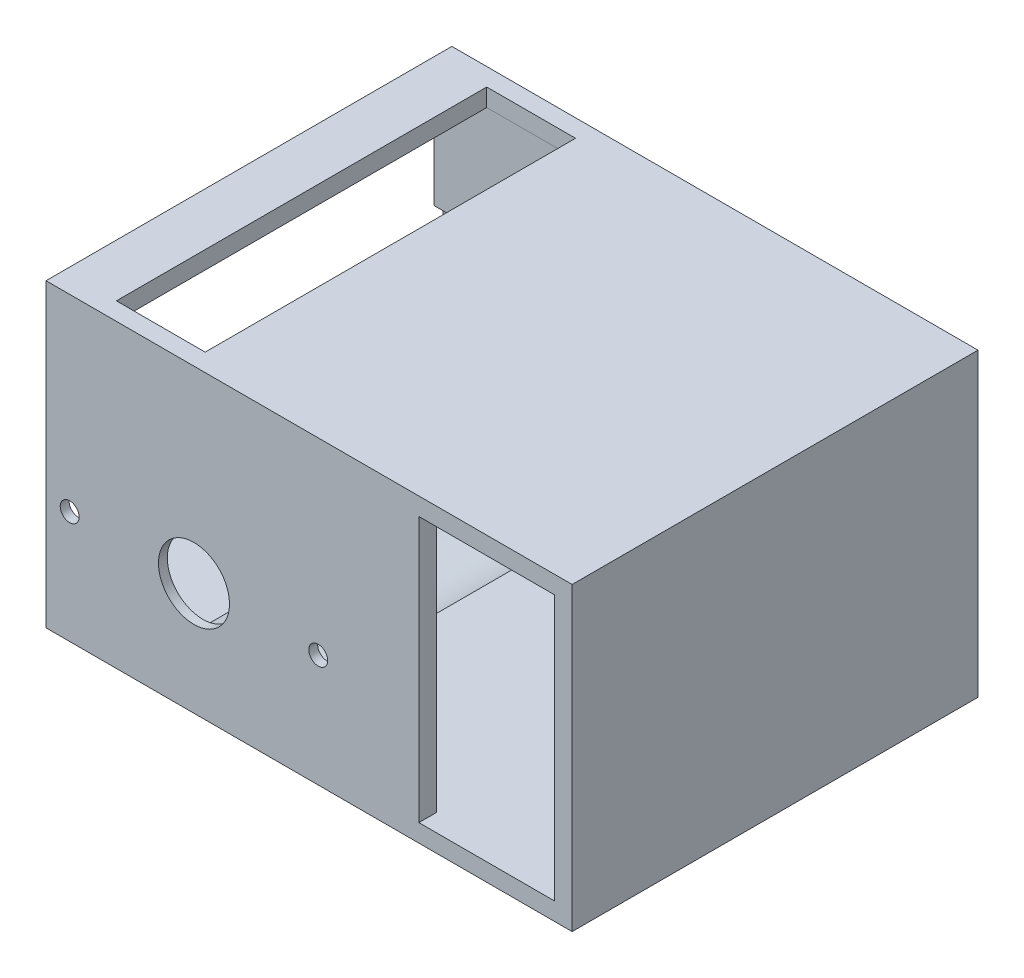
SolidWorks part; units mm, degrees
ref_plane "Front Plane" through (0, 0, 0) normal (0, 0, 1) x (1, 0, 0)
ref_plane "Top Plane" through (0, 0, 0) normal (0, 1, 0) x (1, 0, 0)
ref_plane "Right Plane" through (0, 0, 0) normal (1, 0, 0) x (0, 0, -1)
sketch "Sketch1" plane through (0, 0, 0) normal (0, 0, 1) x (1, 0, 0)
  line L1 (0, 0) -> (88.9, 0)
  line L2 (0, 0) -> (0, 50.8)
  line L3 (0, 50.8) -> (88.9, 50.8)
  line L4 (88.9, 0) -> (88.9, 50.8)
extrude "Boss-Extrude1" add sketch "Sketch1" along normal blind 68.58
sketch "Sketch2" plane through (0, 0, 68.58) normal (0, 0, 1) x (1, 0, 0)
  line L3 (63, 47.8) -> (85.9, 47.8)
  line L4 (63, 47.8) -> (63, 3)
  line L5 (63, 3) -> (85.9, 3)
  line L6 (85.9, 47.8) -> (85.9, 3)
  circle A0 centre (25, 19) radius 6
  circle A1 centre (4, 19) radius 1.6
  circle A2 centre (46, 19) radius 1.6
shell "Shell10" thickness 3
sketch "Sketch4" plane through (0, 0, 0) normal (-1, 0, 0) x (0, 0, 1)
  line L1 (3, 47.8) -> (65.58, 47.8)
  line L2 (3, 47.8) -> (3, 3)
  line L3 (3, 3) -> (65.58, 3)
  line L4 (65.58, 47.8) -> (65.58, 3)
extrude "Cut-Extrude2" cut sketch "Sketch4" against normal blind 10
extrude "Cut-Extrude3" cut sketch "Sketch2" against normal blind 68.59
sketch "Sketch5" plane through (0, 0, 65.58) normal (0, 0, -1) x (-1, 0, 0)
  circle A0 centre (-25, 19) radius 18.3
extrude "Cut-Extrude4" cut sketch "Sketch5" along normal blind 62.58
sketch "Sketch10" plane through (0, 0, 65.58) normal (0, 0, -1) x (-1, 0, 0)
  line L0 (0, 3) -> (0, 47.8) construction
  line L1 (0, 9) -> (-50, 9)
  line L2 (0, 9) -> (0, 29)
  line L3 (0, 29) -> (-50, 29)
  line L4 (-50, 9) -> (-50, 29)
  circle A0 centre (-25, 19) radius 18
  line M4 (0, 3) -> (0, 47.8)
  circle M7 centre (-25, 19) radius 6
  circle M8 centre (-4, 19) radius 1.6
  circle M9 centre (-46, 19) radius 1.6
extrude "Cut-Extrude7" cut sketch "Sketch10" against normal blind 1.5 contours L1 A0 | L3 A0 L1 M7 | L3 A0 | A0 L3 L4 L1 M9 | A0 L1 L3 M4 M8 region at (5.0167, 9.2238, 65.58) region at (25, 5.73, 65.58) region at (25, 9.4118, 65.58) region at (44.9833, 9.2238, 65.58) region at (25, 32.27, 65.58)
extrude "Cut-Extrude8" cut sketch "Sketch10<8>" along normal blind 64.08 contours L1 A0 | L3 A0 L1 M7 | A0 L1 L3 M4 M8 | L3 A0 | A0 L3 L4 L1 M9 region at (5.0167, 9.2238, 65.58) region at (25, 5.73, 65.58) region at (25, 9.4118, 65.58) region at (44.9833, 9.2238, 65.58) region at (25, 32.27, 65.58)
sketch "Sketch10<8>" plane through (0, 0, 65.58) normal (0, 0, -1) x (-1, 0, 0) same geometry as "Sketch10"
sketch "Sketch12" plane through (0, 50.8, 0) normal (0, 1, 0) x (1, 0, 0)
  line L1 (8.8918, -3.0007) -> (23.8951, -3.0007)
  line L2 (8.8918, -3.0007) -> (8.8918, -65.58)
  line L3 (8.8918, -65.58) -> (23.8951, -65.58)
  line L4 (23.8951, -3.0007) -> (23.8951, -65.58)
extrude "Cut-Extrude9" cut sketch "Sketch12" against normal blind 3
